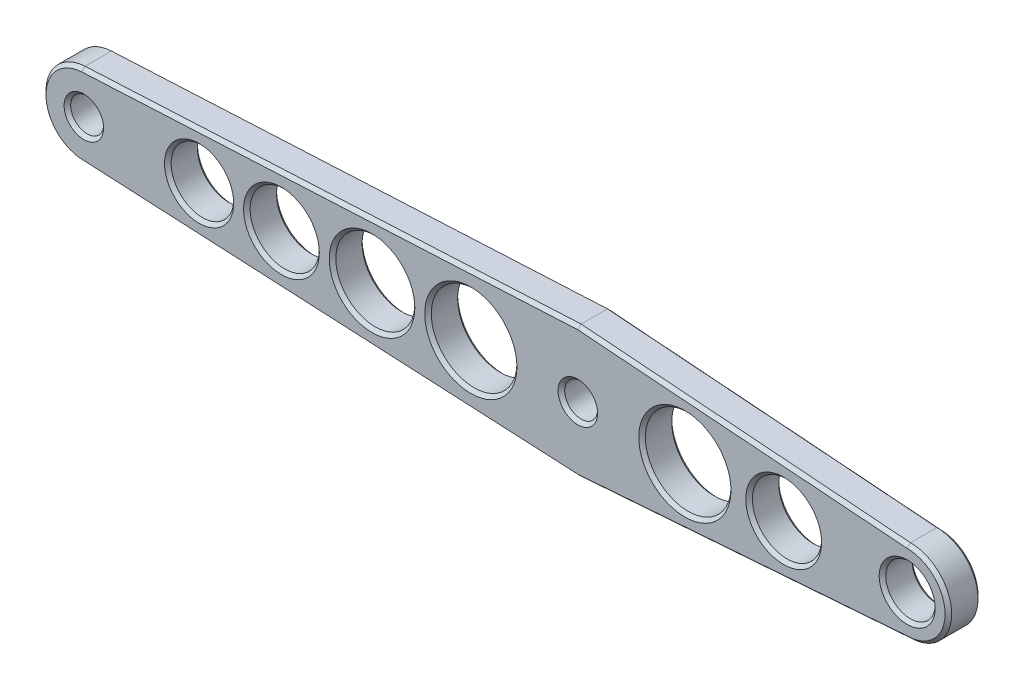
SolidWorks part; units mm, degrees
ref_plane "Front Plane" through (0, 0, 0) normal (0, 0, 1) x (1, 0, 0)
ref_plane "Top Plane" through (0, 0, 0) normal (0, 1, 0) x (1, 0, 0)
ref_plane "Right Plane" through (0, 0, 0) normal (1, 0, 0) x (0, 0, -1)
sketch "Sketch1" plane through (0, 0, 0) normal (0, 0, 1) x (1, 0, 0)
  line L0 (-30.1246, 2.4969) -> (0, 4)
  line L1 (0, 4) -> (20, 2.5008)
  line L2 (20, -2.5008) -> (0, -4)
  line L3 (0, -4) -> (-30, -2.5)
  line L4 (0, 4) -> (0, -4) construction
  line L5 (-30, 0) -> (20, 0) construction
  arc A0 (-30.1246, 2.4969) -> (-30, -2.5) centre (-30, 0) ccw
  arc A1 (20, 2.5008) -> (20, -2.5008) centre (20, 0) cw
  circle A2 centre (0, 0) radius 1
  circle A3 centre (20, 0) radius 1.5
  circle A4 centre (-30, 0) radius 1
  circle A5 centre (-23, 0) radius 1.9
  circle A6 centre (-18, 0) radius 2.1
  circle A7 centre (-12.5, 0) radius 2.4
  circle A8 centre (-6.5, 0) radius 2.6
  circle A9 centre (6.5, 0) radius 2.6
  circle A10 centre (12.5, 0) radius 2.1
  point P13 (-32.4992, -0.0623)
  point P14 (22.5008, 0)
  dimension "D1" = 5
  dimension "D2" = 30
  dimension "D6" = 2
  dimension "D7" = 3.8
  dimension "D8" = 4.2
  dimension "D9" = 4.8
  dimension "D10" = 5.2
  dimension "D11" = 2
  dimension "D12" = 5.2
  dimension "D13" = 4.2
  dimension "D14" = 3
  dimension "D3" = 20
  dimension "D4" = 55
  dimension "D5" = 8
  dimension "D15" = 5
  dimension "D16" = 6
  dimension "D17" = 5.5
  dimension "D18" = 7
  dimension "D19" = 7.5
  dimension "D20" = 6
extrude "Boss-Extrude1" add sketch "Sketch1" along normal blind 2
chamfer "Chamfer1" distance 0.2 angle 45 30 edges at (14.6, 0, 0) (9.1, 0, 0) (-3.9, 0, 0) (-10.1, 0, 0) (-15.9, 0, 0) (-21.1, 0, 0) (-29, 0, 0) (21.5, 0, 0) (1, 0, 0) (-15, -3.25, 0) (10, -3.2504, 0) (22.5008, 0, 0) (10, 3.2504, 0) (-15.0623, 3.2484, 0) (-32.4992, -0.0623, 0) (14.6, 0, 2) (-3.9, 0, 2) (-15.9, 0, 2) (-29, 0, 2) (1, 0, 2) (-15.0623, 3.2484, 2) (10, 3.2504, 2) (22.5008, 0, 2) (10, -3.2504, 2) (-15, -3.25, 2) (-32.4992, -0.0623, 2) (21.5, 0, 2) (-21.1, 0, 2) (-10.1, 0, 2) (9.1, 0, 2)
